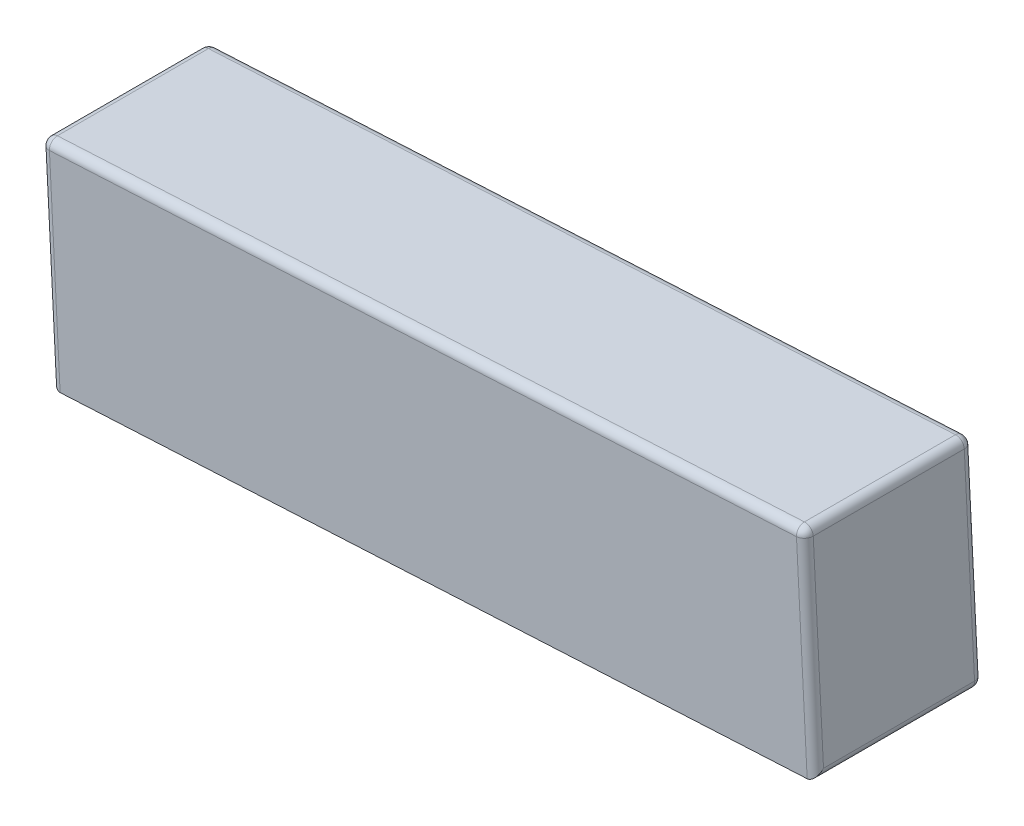
SolidWorks part; units mm, degrees
ref_plane "Front Plane" through (0, 0, 0) normal (0, 0, 1) x (1, 0, 0)
ref_plane "Top Plane" through (0, 0, 0) normal (0, 1, 0) x (1, 0, 0)
ref_plane "Right Plane" through (0, 0, 0) normal (1, 0, 0) x (0, 0, -1)
sketch "Sketch1" plane through (0, 0, 0) normal (0, 0, 1) x (1, 0, 0)
  line L0 (0, 0) -> (2.6534, -50.6945)
  line L1 (2.6534, -50.6945) -> (184.7, -41.1659)
  line L2 (184.7, -41.1659) -> (182.0466, 9.5286)
  line L3 (182.0466, 9.5286) -> (0, 0)
extrude "Boss-Extrude1" add sketch "Sketch1" along normal blind 40
fillet "Fillet1" radius 2 6 edges at (183.3733, -15.8186, 0) (183.3733, -15.8186, 40) (184.7, -41.1659, 20) (91.0233, 4.7643, 0) (182.0466, 9.5286, 20) (91.0233, 4.7643, 40)
fillet "Fillet2" radius 2 8 edges at (1.379, -26.3459, 40) (0.0306, -0.585, 39.4142) (0.0306, -0.585, 0.5858) (184.0844, -40.6115, 0.5858) (0, 0, 20) (2.6534, -50.6945, 20) (1.379, -26.3459, 0) (92.6781, -45.9825, 0)
